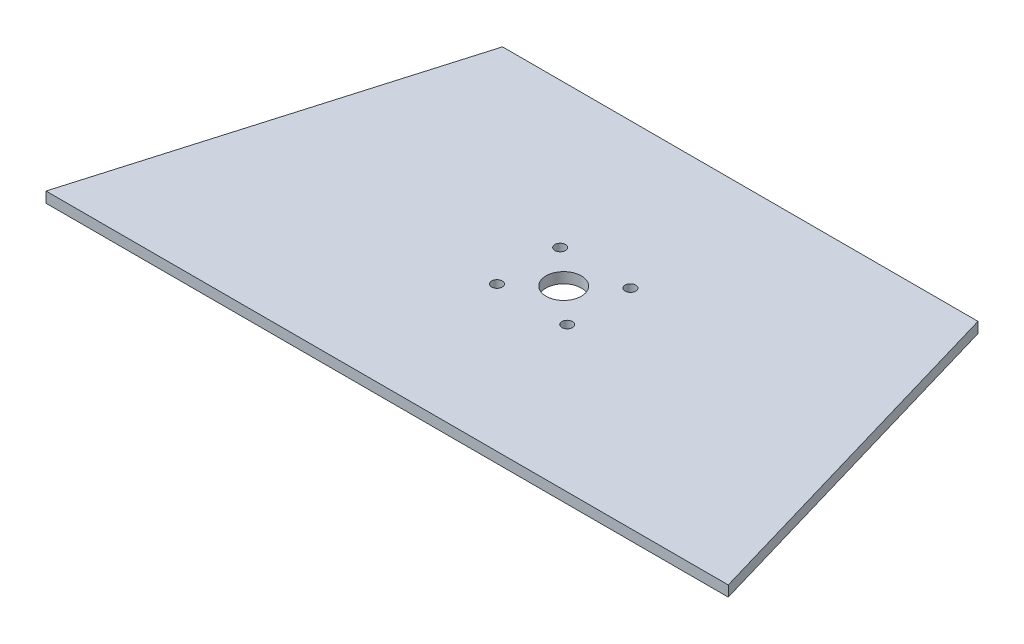
SolidWorks part; units mm, degrees
ref_plane "Front Plane" through (0, 0, 0) normal (0, 0, 1) x (1, 0, 0)
ref_plane "Top Plane" through (0, 0, 0) normal (0, 1, 0) x (1, 0, 0)
ref_plane "Right Plane" through (0, 0, 0) normal (1, 0, 0) x (0, 0, -1)
sketch "Sketch1" plane through (0, 0, 0) normal (0, 1, 0) x (1, 0, 0)
  line L0 (-13.2, 0) -> (180, 0)
  line L3 (90, 0) -> (90, 100) construction
  line L5 (-13.2, 0) -> (16.0799, 100)
  line L6 (180, 0) -> (150.7201, 100)
  line L7 (16.0799, 100) -> (150.7201, 100)
extrude "Boss-Extrude1" add sketch "Sketch1" along normal blind 3
hole_wizard "Ø10.0mm Dowel Hole1" positions "Sketch2" profile "Sketch3" hole size "Ø10.0" standard "ANSI Metric" end condition up to next
sketch "Sketch2" plane through (0, 3, 0) normal (0, 1, 0) x (1, 0, 0)
  point P0 (83.4, 50)
  point P4 (0, 0)
sketch "Sketch3" plane through (83.4, 3, -50) normal (1, 0, 0) x (0, 0, 1)
  line L0 (0, 0) -> (0, 3)
  line L1 (0, 3) -> (5, 3)
  line L2 (5, 3) -> (5, 0)
  line L5 (5, 0) -> (0, 0)
  line L11 (0, -6.35) -> (0, 107.95) construction
  dimension "Thru Hole Dia." = 10
  dimension "Thru Hole Depth" = 3
hole_wizard "Ø3.0mm Dowel Hole1" positions "Sketch4" profile "Sketch5" hole size "Ø3.0" standard "ANSI Metric" end condition up to next
sketch "Sketch4" plane through (0, 3, 0) normal (0, 1, 0) x (1, 0, 0)
  point P0 (73.45, 58.95)
  point P3 (73.45, 41.05)
  point P6 (93.35, 41.05)
  point P9 (93.35, 58.95)
  point P14 (0, 0)
  point P15 (0, 0)
  point P16 (0, 0)
  point P17 (0, 0)
sketch "Sketch5" plane through (73.45, 3, -58.95) normal (1, 0, 0) x (0, 0, 1)
  line L0 (0, 0) -> (0, 3)
  line L1 (0, 3) -> (1.5, 3)
  line L2 (1.5, 3) -> (1.5, 0)
  line L5 (1.5, 0) -> (0, 0)
  line L11 (0, -6.35) -> (0, 107.95) construction
  dimension "Thru Hole Dia." = 3
  dimension "Thru Hole Depth" = 3
